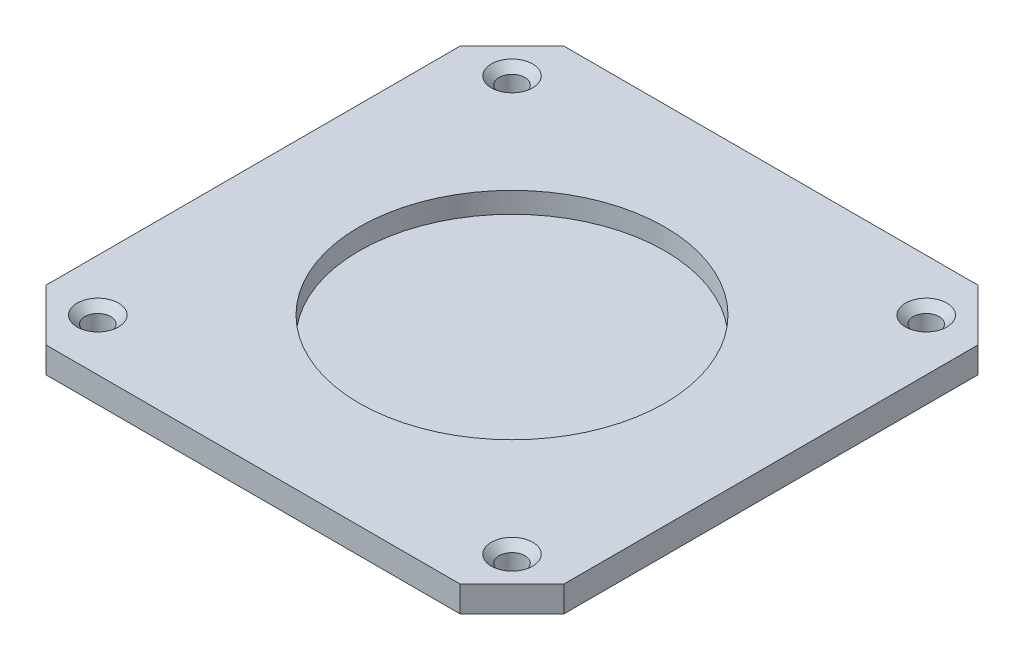
SolidWorks part; units mm, degrees
ref_plane "Front Plane" through (0, 0, 0) normal (0, 0, 1) x (1, 0, 0)
ref_plane "Top Plane" through (0, 0, 0) normal (0, 1, 0) x (1, 0, 0)
ref_plane "Right Plane" through (0, 0, 0) normal (1, 0, 0) x (0, 0, -1)
sketch "Sketch1" plane through (0, 0, 0) normal (0, 1, 0) x (1, 0, 0)
  line L1 (-50, -50) -> (50, -50)
  line L2 (-50, -50) -> (-50, 50)
  line L3 (-50, 50) -> (50, 50)
  line L4 (50, -50) -> (50, 50)
  line L5 (-50, -50) -> (50, 50) construction
  line L6 (-50, 50) -> (50, -50) construction
  circle A0 centre (0, 0) radius 29.5
  circle A1 centre (-40, 40) radius 2.5
  circle A2 centre (40, -40) radius 2.5
  circle A3 centre (40, 40) radius 2.5
  circle A4 centre (-40, -40) radius 2.5
  point P15 (0, 0)
  dimension "D2" = 59
  dimension "D3" = 5
  dimension "D1" = 100
  dimension "D4" = 80
extrude "Boss-Extrude1" add sketch "Sketch1" along normal blind 5 contours L1 L4 L3 L2 A2 A1 A0 A3 A4 region at (-48.5858, 0, 0)
extrude "Boss-Extrude2" add sketch "Sketch1<3>" along normal blind 1 contours A0 region at (0, 0, 0)
sketch "Sketch1<3>" plane through (0, 0, 0) normal (0, 1, 0) x (1, 0, 0) same geometry as "Sketch1"
chamfer "Chamfer1" distance 10 angle 45 4 edges at (-50, 2.5, -50) (50, 2.5, -50) (50, 2.5, 50) (-50, 2.5, 50)
chamfer "Chamfer3" distance 1.5 angle 45 4 edges at (-40, 5, 42.5) (40, 5, 42.5) (40, 5, -37.5) (-40, 5, -37.5)
